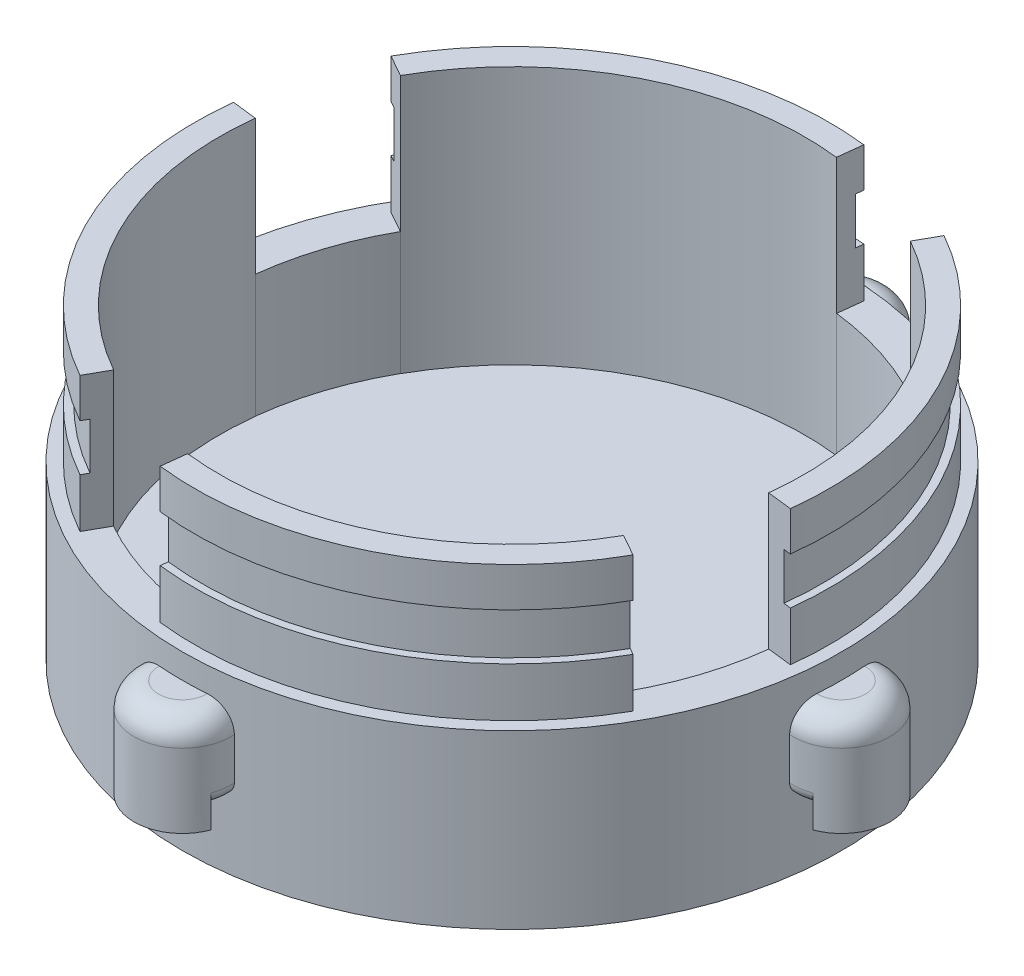
SolidWorks part; units mm, degrees
ref_plane "Front Plane" through (0, 0, 0) normal (0, 0, 1) x (1, 0, 0)
ref_plane "Top Plane" through (0, 0, 0) normal (0, 1, 0) x (1, 0, 0)
ref_plane "Right Plane" through (0, 0, 0) normal (1, 0, 0) x (0, 0, -1)
sketch "Sketch1" plane through (0, 0, 0) normal (0, 1, 0) x (1, 0, 0)
  circle A0 centre (0, 0) radius 30.1625
  circle A1 centre (0, 0) radius 26.9875
sketch "Sketch3" plane through (0, 0, 0) normal (0, 1, 0) x (1, 0, 0)
  line L0 (30.226, 0) -> (34.036, 0) construction
  circle A0 centre (0, 0) radius 34.036
  circle A1 centre (0, 0) radius 30.226
  dimension "D1" = 60.452
  dimension "D2" = 3.81
extrude "Boss-Extrude2" add sketch "Sketch3" along normal blind 12.7 separate body
sketch "Sketch5" plane through (0, 0, 0) normal (0, 1, 0) x (1, 0, 0)
  line L0 (28.559, -16.0622) -> (26.3304, -14.8087)
  line L1 (0, 0) -> (32.5458, -3.792) construction
  line L2 (-3.4981, -30.0058) -> (-3.792, -32.5458)
  line L3 (-16.0622, -28.559) -> (-14.8087, -26.3304)
  line L4 (-30.0058, 3.4981) -> (-32.5458, 3.792)
  line L5 (-28.559, 16.0622) -> (-26.3304, 14.8087)
  line L6 (3.4981, 30.0058) -> (3.792, 32.5458)
  line L7 (0, 0) -> (3.792, 32.5458) construction
  line L8 (0, 0) -> (-28.559, 16.0622) construction
  line L9 (0, 0) -> (-32.5458, 3.792) construction
  line L10 (-32.5458, 3.792) -> (-32.5902, 3.8035)
  line L11 (0, 0) -> (-16.0622, -28.559) construction
  line L12 (0, 0) -> (-3.792, -32.5458) construction
  line L13 (28.559, -16.0622) -> (0, 0) construction
  line L14 (30.0058, -3.4981) -> (32.5458, -3.792)
  line L15 (0, 0) -> (16.0622, 28.559) construction
  line L16 (16.0622, 28.559) -> (14.8087, 26.3304)
  arc A0 (-3.4981, -30.0058) -> (26.3304, -14.8087) centre (0, 0) ccw
  arc A1 (28.559, -16.0622) -> (-3.792, -32.5458) centre (0, 0) cw
  arc A2 (-30.0058, 3.4981) -> (-14.8087, -26.3304) centre (0, 0) ccw
  arc A3 (-16.0622, -28.559) -> (-32.5458, 3.792) centre (0, 0) cw
  arc A4 (3.4981, 30.0058) -> (-26.3304, 14.8087) centre (0, 0) ccw
  arc A5 (-28.559, 16.0622) -> (3.792, 32.5458) centre (0, 0) cw
  arc A12 (30.0058, -3.4981) -> (14.8087, 26.3304) centre (0, 0) ccw
  arc A13 (16.0622, 28.559) -> (32.5458, -3.792) centre (0, 0) cw
  point P16 (0, 0)
  point P31 (0, 0)
  dimension "D1" = 2.54
  dimension "D2" = 4
extrude "Boss-Extrude6" add sketch "Sketch5" along normal blind 26.67 separate body contours A1 L0 A0 L2 | A5 L5 A4 L6 | A3 L3 A2 L4 | A12 L16 A13 L14 region at (14.7075, 0, 28.865) region at (-28.865, 0, 14.7075) region at (-14.7075, 0, -28.865)
sketch "Sketch7" plane through (0, 0, 0) normal (0, 1, 0) x (1, 0, 0)
  line L0 (32.004, 0) -> (34.036, 0) construction
  circle A0 centre (0, 0) radius 34.036
  circle A1 centre (0, 0) radius 32.004
  dimension "D1" = 68.072
  dimension "D2" = 2.032
extrude "Cut-Extrude2" cut sketch "Sketch7" along normal blind 4.826 from offset 17.78
sketch "Sketch8" plane through (0, 0, 0) normal (0, 1, 0) x (1, 0, 0)
  circle A0 centre (0, 0) radius 34.036
  circle A1 centre (0, 0) radius 5
  dimension "D1" = 68.072
  dimension "D2" = 10
extrude "Boss-Extrude7" add sketch "Sketch8" against normal blind 5.08
sketch "Sketch10" plane through (0, 0, 0) normal (0, 1, 0) x (1, 0, 0)
  line L0 (32.004, 0) -> (34.036, 0) construction
  circle A0 centre (0, 0) radius 34.036
  circle A1 centre (0, 0) radius 32.004
  arc A2 (0, -39.0412) -> (4.9916, -33.668) centre (0, -34.036) ccw
  arc A3 (0, -39.0412) -> (-4.9916, -33.668) centre (0, -34.036) cw
  arc A4 (-39.0412, 0) -> (-33.668, 4.9916) centre (-34.036, 0) cw
  arc A5 (-39.0412, 0) -> (-33.668, -4.9916) centre (-34.036, 0) ccw
  arc A6 (0, 39.0412) -> (4.9916, 33.668) centre (0, 34.036) cw
  arc A7 (0, 39.0412) -> (-4.9916, 33.668) centre (0, 34.036) ccw
  arc A8 (39.0412, 0) -> (33.668, -4.9916) centre (34.036, 0) cw
  arc A9 (39.0412, 0) -> (33.668, 4.9916) centre (34.036, 0) ccw
  point P24 (0, 0)
  dimension "D1" = 68.072
  dimension "D2" = 2.032
extrude "Boss-Extrude8" add sketch "Sketch10" along normal blind 10.16 contours A4 A5 A0 | A3 A2 A0 | A8 A9 A0 | A6 A7 A0 region at (36.0926, 0, 0) region at (0, 0, -36.0926) region at (0, 0, 36.0926) region at (-36.0926, 0, 0)
fillet "Fillet1" radius 2.54 4 edges at (39.0412, 10.16, 0) (0, 10.16, -39.0412) (-39.0412, 10.16, 0) (0, 10.16, 39.0412)
sketch "Sketch11" plane through (0, 0, 0) normal (0, 1, 0) x (1, 0, 0)
  line L0 (36.068, 0) -> (34.036, 0) construction
  circle A0 centre (0, 0) radius 34.036
  circle A1 centre (0, 0) radius 36.068
  point P24 (0, 0)
  dimension "D1" = 68.072
  dimension "D2" = 2.032
extrude "Cut-Extrude3" cut sketch "Sketch11" along normal blind 2.032
fillet "Fillet2" radius 1.27 8 edges at (-4.9568, 2.032, -34.7299) (4.9568, 2.032, -34.7299) (-34.7299, 2.032, 4.9568) (-34.7299, 2.032, -4.9568) (4.9568, 2.032, 34.7299) (-4.9568, 2.032, 34.7299) (34.7299, 2.032, 4.9568) (34.7299, 2.032, -4.9568)
